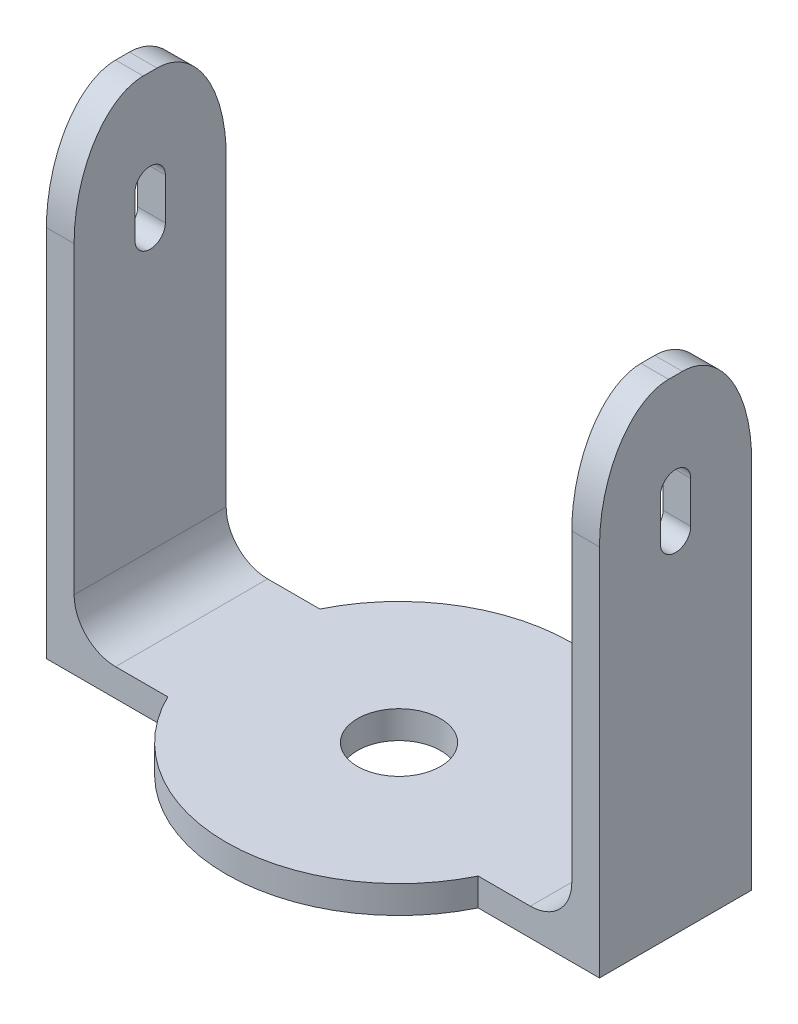
SolidWorks part; units mm, degrees
ref_plane "前视基准面" through (0, 0, 0) normal (0, 0, 1) x (1, 0, 0)
ref_plane "上视基准面" through (0, 0, 0) normal (0, 1, 0) x (1, 0, 0)
ref_plane "右视基准面" through (0, 0, 0) normal (1, 0, 0) x (0, 0, -1)
sketch "草图1" plane through (0, 0, 0) normal (0, 1, 0) x (1, 0, 0)
  line L0 (-11.225, 5.5) -> (-18, 5.5)
  line L1 (18, -5.5) -> (11.225, -5.5)
  line L2 (18, -5.5) -> (18, 5.5)
  line L3 (18, 5.5) -> (11.225, 5.5)
  line L4 (-18, -5.5) -> (-18, 5.5)
  line L5 (18, -5.5) -> (-18, 5.5) construction
  line L6 (18, 5.5) -> (-18, -5.5) construction
  line L7 (-11.225, -5.5) -> (-18, -5.5)
  arc A0 (-11.225, -5.5) -> (11.225, -5.5) centre (0, 0) ccw
  circle A1 centre (0, 0) radius 3
  arc A2 (11.225, 5.5) -> (-11.225, 5.5) centre (0, 0) ccw
  dimension "D1" = 25
  dimension "D4" = 6
  dimension "D2" = 36
  dimension "D3" = 11
extrude "凸台-拉伸1" add sketch "草图1" along normal blind 2
sketch "草图2" plane through (0, 0, 0) normal (0, 1, 0) x (1, 0, 0)
  line L1 (-20, 5.5) -> (-18, 5.5)
  line L2 (-20, 5.5) -> (-20, -5.5)
  line L3 (-20, -5.5) -> (-18, -5.5)
  line L4 (-18, 5.5) -> (-18, -5.5)
  line L5 (11.225, -5.5) -> (18, -5.5) construction
  line L6 (20, 5.5) -> (18, 5.5)
  line L7 (20, 5.5) -> (20, -5.5)
  line L8 (20, -5.5) -> (18, -5.5)
  line L9 (18, 5.5) -> (18, -5.5)
  line L10 (-18, 5.5) -> (-18, -5.5) construction
  line L11 (-11.225, 5.5) -> (-18, 5.5) construction
  line L12 (-18, -5.5) -> (-11.225, -5.5) construction
  line L13 (18, -5.5) -> (18, 5.5) construction
  line L14 (18, 5.5) -> (11.225, 5.5) construction
  line L15 (18, 5.5) -> (11.225, 5.5) construction
  dimension "D1" = 2
  dimension "D2" = 2
extrude "凸台-拉伸2" add sketch "草图2" along normal blind 35
fillet "圆角1" radius 8 4 edges at (19, 35, -5.5) (19, 35, 5.5) (-19, 35, -5.5) (-19, 35, 5.5) second distance 5 first distance on face at (16.4083, 12.3333, -5.5) first distance on face at (16.4083, 12.3333, 5.5) first distance on face at (-16.4083, 12.3333, -5.5) first distance on face at (-16.4083, 12.3333, 5.5)
sketch "草图3" plane through (-20, 0, 0) normal (-1, 0, 0) x (0, 0, 1)
  line L0 (1.1, 28) -> (1.1, 25)
  line L2 (-1.1, 25) -> (-1.1, 28)
  arc A1 (1.1, 28) -> (-1.1, 28) centre (0, 28) ccw
  arc A2 (-1.1, 25) -> (1.1, 25) centre (0, 25) ccw
  dimension "D1" = 3
  dimension "D2" = 2.2
  dimension "D3" = 2.2
  dimension "D4" = 25
extrude "切除-拉伸1" cut sketch "草图3" against normal through all both and the other way through all
fillet "圆角2" radius 3 2 edges at (-18, 2, 0) (18, 2, 0)
